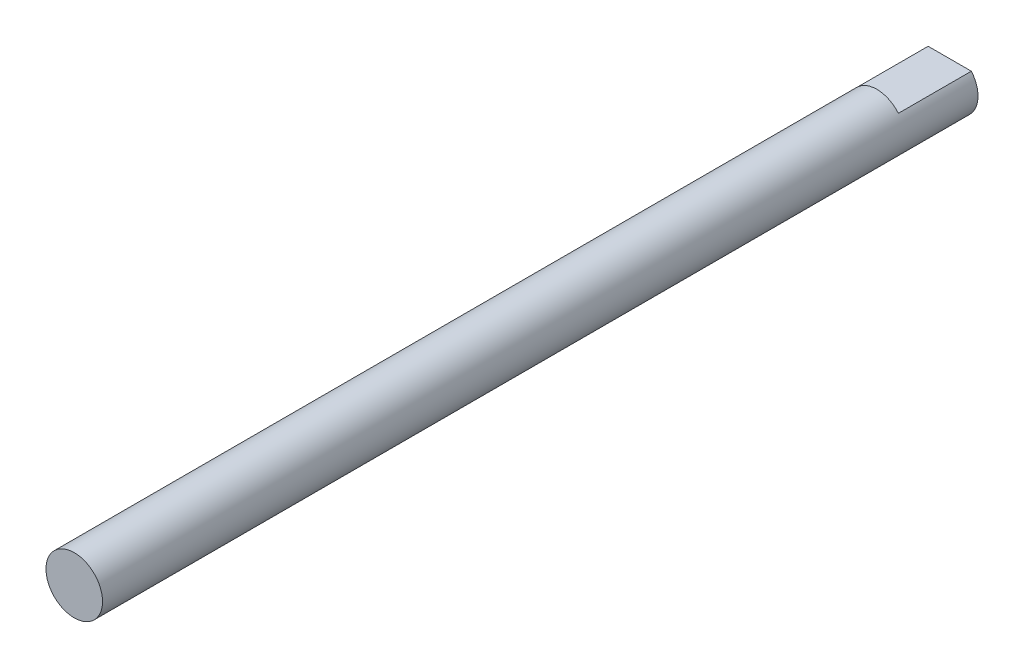
SolidWorks part; units mm, degrees
ref_plane "Front Plane" through (0, 0, 0) normal (0, 0, 1) x (1, 0, 0)
ref_plane "Top Plane" through (0, 0, 0) normal (0, 1, 0) x (1, 0, 0)
ref_plane "Right Plane" through (0, 0, 0) normal (1, 0, 0) x (0, 0, -1)
sketch "Sketch2" plane through (0, 0, 0) normal (0, 0, 1) x (1, 0, 0)
  circle A0 centre (0, 0) radius 3.875
  dimension "D1" = 7.75
extrude "Boss-Extrude1" add sketch "Sketch2" along normal blind 120
sketch "Sketch3" plane through (0, 0, 0) normal (0, 0, 1) x (1, 0, 0)
  line L0 (-2.9607, 2.5) -> (2.9607, 2.5)
  circle A0 centre (0, 0) radius 3.875 construction
  arc A1 (2.9607, 2.5) -> (-2.9607, 2.5) centre (0, 0) ccw
  point P7 (0, 0)
  dimension "D1" = 2.5
extrude "Cut-Extrude1" cut sketch "Sketch3" along normal blind 10
